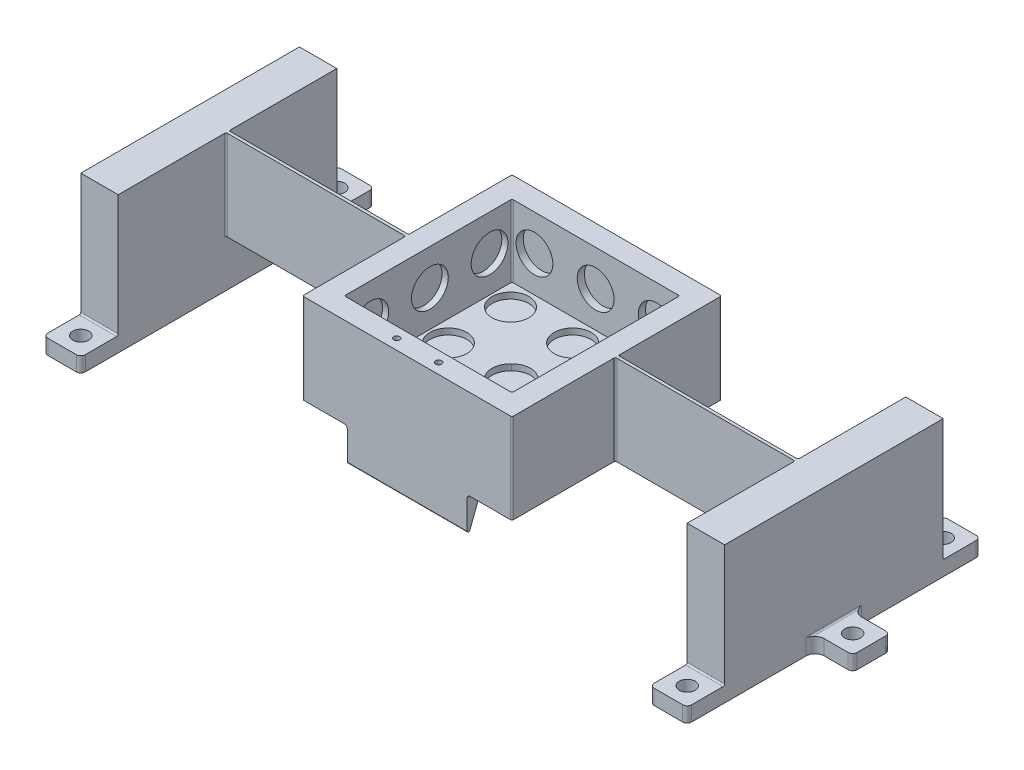
SolidWorks part; units mm, degrees
ref_plane "Front Plane" through (0, 0, 0) normal (0, 0, 1) x (1, 0, 0)
ref_plane "Top Plane" through (0, 0, 0) normal (0, 1, 0) x (1, 0, 0)
ref_plane "Right Plane" through (0, 0, 0) normal (1, 0, 0) x (0, 0, -1)
sketch "Sketch1" plane through (0, 0, 0) normal (0, 1, 0) x (1, 0, 0)
  line L1 (-35, -35) -> (35, -35)
  line L2 (-35, -35) -> (-35, 35)
  line L3 (-35, 35) -> (35, 35)
  line L4 (35, -35) -> (35, 35)
  line L5 (-35, -35) -> (35, 35) construction
  line L6 (-35, 35) -> (35, -35) construction
  point P0 (0, 0)
  dimension "D1" = 70
  dimension "D2" = 70
extrude "Boss-Extrude1" add sketch "Sketch1" along normal blind 30
shell "Shell1" thickness 7 removed face at (0, 30, 0)
sketch "Sketch2" plane through (0, 30, 0) normal (0, 1, 0) x (1, 0, 0)
  line L0 (-35, 35) -> (-35, -35) construction
  line L1 (-28, -28) -> (28, -28) construction
  line L2 (-28, -28) -> (-28, 28) construction
  line L3 (-28, 28) -> (28, 28) construction
  line L4 (28, -28) -> (28, 28) construction
  line L5 (-28, -28) -> (28, 28) construction
  line L6 (-28, 28) -> (28, -28) construction
  line L7 (35, 35) -> (-35, 35) construction
  point P0 (0, 0)
  dimension "D1" = 7
  dimension "D2" = 7
sketch "Sketch3" plane through (35, 0, 0) normal (1, 0, 0) x (0, 0, -1)
  line L0 (-35, 30) -> (35, 30) construction
  line L1 (-24, 30) -> (-23, 30) construction
  line L2 (-24, 30) -> (-24, 0) construction
  line L3 (-24, 0) -> (-23, 0) construction
  line L4 (-23, 30) -> (-23, 0) construction
  line L5 (-35, 0) -> (35, 0) construction
  line L6 (-28, 30) -> (28, 30) construction
  line L7 (-0.5, 30) -> (0.5, 30)
  line L8 (-0.5, 30) -> (-0.5, 0)
  line L9 (-0.5, 0) -> (0.5, 0)
  line L10 (0.5, 30) -> (0.5, 0)
  line L11 (28, 30) -> (-28, 30) construction
  line L12 (24, 30) -> (23, 30) construction
  line L13 (24, 30) -> (24, 0) construction
  line L14 (24, 0) -> (23, 0) construction
  line L15 (23, 30) -> (23, 0) construction
  line L16 (-23.5, 30) -> (-23.5, 0) construction
  line L17 (0, 30) -> (0, 0) construction
  line L18 (23.5, 0) -> (23.5, 30) construction
  dimension "D1" = 23
  dimension "D2" = 23
  dimension "D3" = 1
extrude "Boss-Extrude2" add sketch "Sketch3" along normal blind 60
sketch "Sketch5" plane through (95, 0, 0) normal (1, 0, 0) x (0, 0, -1)
  line L1 (-36.5, 30) -> (36.5, 30)
  line L2 (-36.5, 30) -> (-36.5, 0)
  line L3 (-36.5, 0) -> (36.5, 0)
  line L4 (36.5, 30) -> (36.5, 0)
  line L5 (28, 30) -> (-28, 30) construction
  line L6 (0.5, 0) -> (35, 0) construction
  line L8 (35, 30) -> (35, 0) construction
  line L9 (-35, 30) -> (-35, 0) construction
  dimension "D1" = 1.5
  dimension "D2" = 1.5
extrude "Boss-Extrude3" add sketch "Sketch5" along normal blind 12.5
sketch "Sketch6" plane through (0, 0, 0) normal (0, -1, 0) x (1, 0, 0)
  line L1 (95, 36.5) -> (107.5, 36.5)
  line L2 (95, 36.5) -> (95, -36.5)
  line L3 (95, -36.5) -> (107.5, -36.5)
  line L4 (107.5, 36.5) -> (107.5, -36.5)
extrude "Boss-Extrude4" add sketch "Sketch6" along normal blind 15.75
sketch "Sketch8" plane through (0, -15.75, 0) normal (0, -1, 0) x (1, 0, 0)
  line L1 (107.5, -36.5) -> (95, -36.5)
  line L2 (107.5, -36.5) -> (107.5, -49)
  line L3 (107.5, -49) -> (95, -49)
  line L4 (95, -36.5) -> (95, -49)
  line L5 (107.5, 36.5) -> (95, 36.5)
  line L6 (107.5, 36.5) -> (107.5, 49)
  line L7 (107.5, 49) -> (95, 49)
  line L8 (95, 36.5) -> (95, 49)
  line L13 (107.5, -36.5) -> (107.5, 36.5) construction
  line L14 (120, -6.25) -> (107.5, -6.25)
  line L15 (120, -6.25) -> (120, 6.25)
  line L16 (120, 6.25) -> (107.5, 6.25)
  line L17 (107.5, -6.25) -> (107.5, 6.25)
  line L18 (120, -6.25) -> (107.5, 6.25) construction
  line L19 (120, 6.25) -> (107.5, -6.25) construction
  line L20 (95, 0) -> (120, 0) construction
  line L21 (95, 0.5) -> (95, -0.5) construction
  point P13 (113.75, 0)
  point P19 (107.5, 0)
  point P20 (107.5, 0)
extrude "Boss-Extrude5" add sketch "Sketch8" against normal blind 5
hole_wizard "Ø5.0mm Dowel Hole1" positions "Sketch9" profile "Sketch10" hole size "Ø5.0" standard "ANSI Metric"
sketch "Sketch9" plane through (0, -10.75, 0) normal (0, 1, 0) x (1, 0, 0)
  line L0 (101.25, 49) -> (101.25, 42.75) construction
  line L1 (95, 49) -> (107.5, 49) construction
  line L2 (101.25, 42.75) -> (107.5, 42.75) construction
  line L3 (107.5, 49) -> (107.5, 36.5) construction
  line L5 (107.5, 0) -> (113.75, 0) construction
  line L6 (107.5, -6.25) -> (107.5, 6.25) construction
  line L7 (113.75, 0) -> (113.75, 6.25) construction
  line L8 (107.5, 6.25) -> (120, 6.25) construction
  line L10 (101.25, -36.5) -> (101.25, -42.75) construction
  line L11 (95, -36.5) -> (107.5, -36.5) construction
  line L12 (101.25, -42.75) -> (107.5, -42.75) construction
  line L13 (107.5, -36.5) -> (107.5, -49) construction
  point P0 (101.25, 42.75)
  point P2 (113.75, 0)
  point P4 (101.25, -42.75)
sketch "Sketch10" plane through (101.25, -10.75, -42.75) normal (1, 0, 0) x (0, 0, 1)
  line L0 (0, 0) -> (0, 18.1023)
  line L1 (0, 18.1023) -> (2.65, 16.51)
  line L2 (2.65, 16.51) -> (2.65, 0)
  line L5 (2.65, 0) -> (0, 0)
  line L10 (0, 18.1023) -> (-2.65, 16.51) construction
  line L11 (0, -6.35) -> (0, 107.95) construction
  dimension "Hole Dia." = 5.3
  dimension "Hole Depth" = 16.51
  dimension "Drill Angle" = 118
mirror "Mirror1" about plane through (0, 0, 0) normal (1, 0, 0) of "Boss-Extrude2", "Boss-Extrude3", "Boss-Extrude5", "Boss-Extrude4", "Ø5.0mm Dowel Hole1"
fillet "Fillet1" radius 0.5 12 edges at (-95, 15, 0.5) (-95, 15, -0.5) (-35, 15, 0.5) (-35, 15, -0.5) (-101.25, -10.75, -36.5) (-101.25, -10.75, 36.5) (35, 15, 0.5) (35, 15, -0.5) (95, 15, 0.5) (95, 15, -0.5) (101.25, -10.75, -36.5) (101.25, -10.75, 36.5)
fillet "Fillet2" radius 1.5 12 edges at (120, -13.25, 6.25) (120, -13.25, -6.25) (107.5, -13.25, -49) (95, -13.25, -49) (107.5, -13.25, 49) (95, -13.25, 49) (-95, -13.25, -49) (-107.5, -13.25, -49) (-120, -13.25, -6.25) (-120, -13.25, 6.25) (-95, -13.25, 49) (-107.5, -13.25, 49)
sketch "Sketch11" plane through (0, 6, 0) normal (0, 1, 0) x (1, 0, 0)
  line L26 (-28, -28) -> (-28, 28) construction
  line L32 (-28, -28) -> (28, -28) construction
  circle A0 centre (-21, -21) radius 6.15
  dimension "D1" = 12.3
  dimension "D2" = 0.85
  dimension "D3" = 0.85
extrude "Cut-Extrude1" cut sketch "Sketch11" against normal blind 2.05
pattern_linear "LPattern1" count 3 spacing 20.75 along (1, 0, 0) count 3 spacing 20.75 along (0, 0, -1) of "Cut-Extrude1"
sketch "Sketch14" plane through (0, 6, 0) normal (0, 1, 0) x (1, 0, 0)
  line L0 (-28, 0) -> (0, 0) construction
  line L1 (-28, 28) -> (-28, -28) construction
  line L2 (0, 0) -> (0, -28) construction
  line L3 (-28, -28) -> (28, -28) construction
  circle A0 centre (0, 0) radius 6.15
  dimension "D1" = 12.3
extrude "Cut-Extrude4" cut sketch "Sketch14" against normal blind 2.05
sketch "Sketch12" plane through (-28, 0, 0) normal (1, 0, 0) x (0, 0, -1)
  line L5 (-28, 18) -> (-19.35, 18) construction
  line L6 (-28, 30) -> (-28, 6) construction
  circle A0 centre (-19.35, 18) radius 6.15
  dimension "D1" = 12.3
  dimension "D2" = 2.5
extrude "Cut-Extrude2" cut sketch "Sketch12" against normal blind 2.05
pattern_linear "LPattern2" count 3 spacing 19.925 along (0, 0, -1) of "Cut-Extrude2"
sketch "Sketch13" plane through (0, 0, -28) normal (0, 0, -1) x (-1, 0, 0)
  line L6 (-28, 30) -> (-28, 6) construction
  line L7 (-20.35, 18) -> (-28, 18) construction
  circle A0 centre (-20.35, 18) radius 6.15
  dimension "D1" = 12.3
  dimension "D3" = 1.5
extrude "Cut-Extrude3" cut sketch "Sketch13" along normal blind 2.4
pattern_linear "LPattern3" count 3 spacing 20.425 along (-1, 0, 0) of "Cut-Extrude3"
mirror "Mirror2" about plane through (0, 0, 0) normal (1, 0, 0) of "LPattern2", "Cut-Extrude2"
fillet "Fillet3" radius 0.5 4 edges at (28, 18, -28) (-28, 18, -28) (28, 18, 28) (-28, 18, 28)
fillet "Fillet4" radius 0.5 4 edges at (-35, 15, 35) (35, 15, 35) (-35, 15, -35) (35, 15, -35)
sketch "Sketch19" plane through (0, 0, 0) normal (1, 0, 0) x (0, 0, -1)
  line L0 (-30, 0) -> (-35, -13.25)
  line L1 (-35, -13.25) -> (-35, 0)
  line L2 (-35, 0) -> (-30, 0)
  line L3 (0, 0) -> (-30, 0) construction
  line L4 (47.5, -15.75) -> (-47.5, -15.75) construction
  dimension "D1" = 5
  dimension "D2" = 35
  dimension "D3" = 2.5
extrude "Boss-Extrude8" add sketch "Sketch19" along normal mid plane 40
sketch "Sketch20" plane through (0, 0, 0) normal (1, 0, 0) x (0, 0, -1)
  line L0 (-35, 20) -> (-42.5, 20)
  line L1 (-42.5, 20) -> (-42.5, 30)
  line L2 (-36.5, 30) -> (-42.5, 30) construction
  line L5 (-42.5, 30) -> (-40, 30)
  line L6 (-40, 30) -> (-40, 22.5)
  line L7 (-40, 22.5) -> (-35, 22.5)
  line L8 (-35, 22.5) -> (-35, 20)
  line L9 (-35, 30) -> (-35, 0) construction
  line L10 (-35, 0) -> (-35, 30) construction
  dimension "D1" = 5
  dimension "D2" = 10
  dimension "D3" = 2.5
  dimension "D4" = 2.5
extrude "Place For Sensor" [suppressed] add sketch "Sketch20" along normal mid plane 10
fillet "Place For Sensor Fillet5" [suppressed] radius 0.5
fillet "Place For Sensor Fillet6" [suppressed] radius 1.5
hole_wizard "Place For Sensor Ø3.0mm Dowel Hole2" [suppressed] positions "Sketch21" profile "Sketch22" hole size "Ø3.0" standard "ANSI Metric"
sketch "Sketch21" [suppressed] plane through (0, 0, 32.5) normal (0, 0, 1) x (1, 0, 0)
  line L0 (-2.5, 27.5) -> (2.5, 27.5) construction
  line L2 (-18, 30) -> (18, 30) construction
  line L3 (-5, 28.5) -> (-5, 20.5) construction
  line L4 (5, 28.5) -> (5, 20.5) construction
  point P0 (-2.5, 27.5)
  point P2 (2.5, 27.5)
  dimension "D1" = 2.5
  dimension "D2" = 2.5
  dimension "D3" = 2.5
sketch "Sketch22" plane through (-2.5, 27.5, 32.5) normal (1, 0, 0) x (0, -1, 0)
  line L0 (0, 0) -> (0, 2.5)
  line L1 (0, 2.5) -> (1.65, 2.5)
  line L2 (1.65, 2.5) -> (1.65, 0)
  line L5 (1.65, 0) -> (0, 0)
  line L11 (0, -6.35) -> (0, 107.95) construction
  dimension "Thru Hole Dia." = 3.3
  dimension "Thru Hole Depth" = 2.5
sketch "Sketch23" plane through (0, 30, 0) normal (0, 1, 0) x (1, 0, 0)
  line L1 (-28, -28) -> (28, -28) construction
  circle A0 centre (-7, -31.5) radius 1
  circle A1 centre (7, -31.5) radius 1
  dimension "D4" = 2
  dimension "D1" = 3.5
  dimension "D2" = 14
  dimension "D3" = 7
extrude "Cut-Extrude5" cut sketch "Sketch23" against normal blind 6
fillet "Fillet5" radius 0.5 1 edges at (0, -13.25, 35)
fillet "Fillet6" radius 1 3 edges at (-20, 0, 32.5) (20, 0, 32.5) (0, 0, 30)
fillet "Fillet8" radius 3 4 edges at (107.5, -13, 6.25) (107.5, -13, -6.25) (-107.5, -13, -6.25) (-107.5, -13, 6.25)
